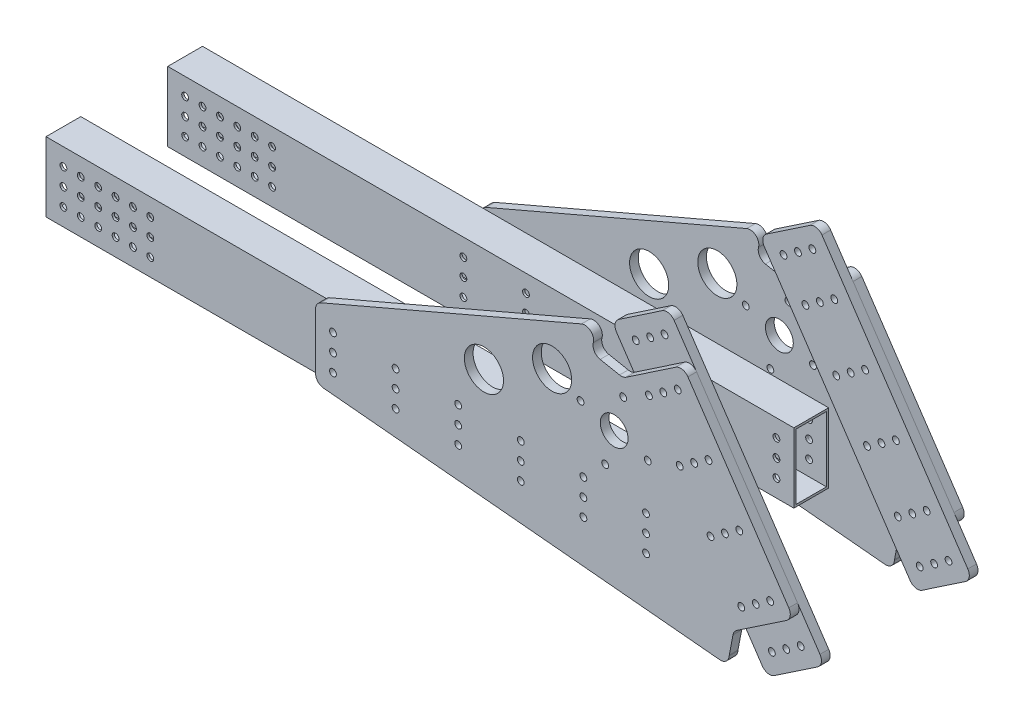
SolidWorks part; units mm, degrees
other "Markup1"
sketch "Sketch2"
sketch "Sketch9" plane through (0, 0, 0) normal (0, 0, 1) x (1, 0, 0)
material "6061-T6 (SS)"
ref_plane "Front Plane" through (0, 0, 0) normal (0, 0, 1) x (1, 0, 0)
ref_plane "Top Plane" through (0, 0, 0) normal (0, 1, 0) x (1, 0, 0)
ref_plane "Right Plane" through (0, 0, 0) normal (1, 0, 0) x (0, 0, -1)
sketch "Grid" plane through (0, 0, 0) normal (0, 0, 1) x (1, 0, 0)
  line L0 (-23.2766, 0) -> (153.3593, 0) construction
  line L1 (0, 0) -> (0, 151.4205) construction
  line L6 (-1009.65, 1168.4) -> (-1009.65, 0) construction
  line L15 (-361.95, 520.7) -> (-803.275, 520.7)
  line L16 (-361.95, 520.7) -> (-361.95, 0)
  line L17 (-361.95, 0) -> (-803.275, 0)
  line L18 (-803.275, 520.7) -> (-803.275, 0)
  line L19 (-803.275, 0) -> (-1244.6, 0)
  line L20 (-803.275, 0) -> (-803.275, 825.5)
  line L21 (-803.275, 825.5) -> (-1244.6, 825.5)
  line L22 (-1244.6, 0) -> (-1244.6, 825.5)
  line L23 (-1030.732, 0) -> (-988.568, 0)
  line L24 (-1030.732, 0) -> (-1030.732, 1168.4)
  line L25 (-1030.732, 1168.4) -> (-988.568, 1168.4)
  line L26 (-988.568, 0) -> (-988.568, 1168.4)
  line L27 (-598.932, 0) -> (-556.768, 0)
  line L28 (-598.932, 0) -> (-598.932, 863.6)
  line L29 (-598.932, 863.6) -> (-556.768, 863.6)
  line L30 (-556.768, 0) -> (-556.768, 863.6)
  line L31 (-577.85, 863.6) -> (-577.85, 0) construction
  line L32 (-361.95, 520.7) -> (-361.95, 596.9) construction
  line L33 (-803.275, 825.5) -> (-803.275, 901.7) construction
  line L34 (-370.0766, 0) -> (-263.7141, 304.8)
  line L35 (-263.7141, 304.8) -> (-157.3516, 0)
  line L36 (-157.3516, 0) -> (-370.0766, 0)
  circle A0 centre (-100.3958, 159.9664) radius 120.65
  dimension "D3" = 241.3
  dimension "D2" = 76.2
  dimension "D4" = 304.8
  dimension "D5" = 212.725
  dimension "D7" = 42.164
  dimension "D8" = 520.7
  dimension "D9" = 304.8
  dimension "D10" = 1168.4
  dimension "D11" = 863.6
  dimension "D12" = 361.95
  dimension "D13" = 577.85
  dimension "D14" = 803.275
  dimension "D15" = 1009.65
sketch "ChassisXY" plane through (0, 0, 0) normal (0, 0, 1) x (1, 0, 0)
  line L0 (755.65, 93.726) -> (95.25, 93.726)
  line L1 (755.65, 93.726) -> (755.65, 42.926)
  line L2 (755.65, 42.926) -> (95.25, 42.926)
  line L3 (95.25, 93.726) -> (95.25, 42.926)
  line L15 (736.7108, 119.126) -> (675.4349, 119.126)
  line L16 (787.4, 42.926) -> (768.35, 42.926)
  line L19 (63.5, 169.926) -> (82.55, 169.926)
  line L20 (736.7108, 119.126) -> (694.5957, 90.719) construction
  line L21 (736.7108, 119.126) -> (717.55, 147.533) construction
  line L22 (694.5957, 90.719) -> (675.4349, 119.126) construction
  line L23 (717.55, 147.533) -> (675.4349, 119.126) construction
  line L27 (63.5, 169.926) -> (63.5, 42.926)
  line L31 (88.9, 42.926) -> (88.9, 1979.9925) construction
  line L32 (62.806, 1979.9925) -> (762, 1979.9925) construction
  line L33 (63.5, 42.926) -> (82.55, 42.926)
  line L36 (88.9, 1320.8) -> (762, 1320.8) construction
  line L37 (88.9, 988.6997) -> (131.0151, 1017.1067) construction
  line L45 (63.5, 42.926) -> (31.75, 42.926)
  line L46 (717.55, 147.533) -> (675.4349, 119.126) construction
  line L47 (717.55, 147.533) -> (-518.4596, 1979.9925) construction
  line L48 (675.4349, 119.126) -> (-560.5747, 1951.5855) construction
  line L49 (-518.4596, 1979.9925) -> (-560.5747, 1951.5855) construction
  line L50 (63.5, 42.926) -> (63.5, 169.926)
  line L51 (0, 74.676) -> (0, 138.176)
  line L52 (31.75, 169.926) -> (63.5, 169.926)
  line L54 (425.45, 93.726) -> (425.45, 42.926) construction
  line L55 (762, 42.926) -> (762, 1979.9925) construction
  line L56 (819.15, 169.926) -> (787.4, 169.926)
  line L57 (850.9, 74.676) -> (850.9, 138.176)
  line L58 (787.4, 42.926) -> (787.4, 169.926)
  line L59 (787.4, 42.926) -> (819.15, 42.926)
  line L60 (82.55, 169.926) -> (82.55, 42.926)
  line L61 (768.35, 169.926) -> (768.35, 42.926)
  line L62 (787.4, 169.926) -> (768.35, 169.926)
  line L63 (787.4, 169.926) -> (787.4, 42.926)
  line L64 (0, 0) -> (0, 200151.4205) construction
  line L65 (-200023.2766, 0) -> (200153.3593, 0) construction
  line L66 (95.25, 152.4) -> (755.65, 152.4) construction
  arc A5 (31.75, 169.926) -> (0, 138.176) centre (31.75, 138.176) ccw
  arc A6 (0, 74.676) -> (31.75, 42.926) centre (31.75, 74.676) ccw
  circle A7 centre (31.75, 74.676) radius 31.75 construction
  circle A8 centre (31.75, 138.176) radius 31.75 construction
  circle A9 centre (819.15, 138.176) radius 31.75 construction
  circle A10 centre (819.15, 74.676) radius 31.75 construction
  arc A11 (850.9, 74.676) -> (819.15, 42.926) centre (819.15, 74.676) cw
  arc A12 (819.15, 169.926) -> (850.9, 138.176) centre (819.15, 138.176) cw
  dimension "D3" = 63.5
  dimension "D1" = 50.8
  dimension "D2" = 56
  dimension "D4" = 38.1
  dimension "D5" = 50.8
  dimension "D6" = 12.7
  dimension "D7" = 19.05
  dimension "D8" = 42.926
  dimension "D9" = 109.474
  dimension "D10" = 25.4
  dimension "D12" = 660.4
  dimension "D13" = 6.35
ref_plane "Plane1" through (561.5696, 378.7835, 0) normal (0.829, 0.5592, 0) x (-0.5592, 0.829, 0)
sketch "carriage geo" plane through (0, 0, 0) normal (0, 0, 1) x (1, 0, 0)
  line L1 (116.0373, 195.326) -> (624.0373, 195.326)
  line L2 (116.0373, 195.326) -> (116.0373, 246.126)
  line L3 (116.0373, 246.126) -> (624.0373, 246.126)
  line L4 (624.0373, 195.326) -> (624.0373, 246.126)
  line L6 (624.0373, 195.326) -> (700.6322, 195.326) construction
  line L17 (717.55, 147.533) -> (-518.4596, 1979.9925) construction
  line L24 (624.0373, 246.126) -> (666.3671, 246.126) construction
  line L33 (666.3671, 246.126) -> (700.6322, 195.326) construction
  line L35 (675.4349, 119.126) -> (-560.5747, 1951.5855) construction
  line L64 (755.65, 93.726) -> (95.25, 93.726) construction
  circle A0 centre (154.1373, 220.726) radius 14.2875
  circle A58 centre (256.8816, 507.741) radius 25.4
  point P4 (353.8882, 537.9448)
  line B0 (120.4355, 364.2548) -> (144.4436, 355.656) construction
  line B1 (345.3934, 565.2279) -> (248.3868, 535.0242)
  line B2 (339.9907, 375.4447) -> (343.9447, 374.0285) construction
  line B3 (348.2442, 386.0326) -> (300.3235, 403.196) construction
  line B4 (308.577, 413.7839) -> (348.5895, 399.4529)
  line B5 (107.1432, 327.1426) -> (206.8255, 291.4401)
  line B6 (112.3162, 360.4178) -> (103.3062, 335.2619)
  line B7 (352.5436, 398.0367) -> (348.5895, 399.4529) construction
  line B8 (366.599, 439.1494) -> (341.413, 442.4393) construction
  line B9 (353.8882, 537.9448) -> (341.413, 442.4393) construction
  line B10 (343.9447, 374.0285) -> (352.5436, 398.0367)
  line B11 (348.5895, 399.4529) -> (308.577, 413.7839)
  line B12 (304.6229, 415.2001) -> (296.0241, 391.1919)
  line B13 (299.9781, 389.7757) -> (339.9907, 375.4447)
  line B14 (140.4752, 344.576) -> (141.8914, 348.5301) construction
  line B15 (129.3385, 325.9381) -> (133.2925, 324.5219) construction
  line B16 (110.7006, 337.0748) -> (109.2844, 333.1207) construction
  line B17 (121.8372, 355.7127) -> (117.8832, 357.1289) construction
  line B18 (117.8832, 357.1289) -> (110.7006, 337.0748)
  line B19 (109.2844, 333.1207) -> (129.3385, 325.9381)
  line B20 (141.8914, 348.5301) -> (121.8372, 355.7127)
  line B21 (133.2925, 324.5219) -> (140.4752, 344.576)
  line B22 (296.0241, 391.1919) -> (299.9781, 389.7757) construction
  line B23 (308.577, 413.7839) -> (304.6229, 415.2001) construction
  arc B24 (248.3868, 535.0242) -> (233.4586, 491.3735) centre (256.8816, 507.741) ccw
  circle B25 centre (256.8816, 507.741) radius 3.1877
  circle B26 centre (353.8882, 537.9448) radius 3.1877
  arc B27 (107.1432, 327.1426) -> (103.3062, 335.2619) centre (109.2844, 333.1207) cw
  circle B28 centre (341.413, 442.4393) radius 30 construction
  arc B29 (121.2422, 363.9009) -> (112.3162, 360.4178) centre (118.2943, 358.2767) ccw
  arc B30 (233.4586, 491.3735) -> (121.2422, 363.9009) centre (161.817, 441.3116) cw
  circle B31 centre (341.413, 442.4393) radius 25.4 construction
  circle B32 centre (366.599, 439.1494) radius 2.4892
  circle B33 centre (338.1231, 417.2533) radius 2.4892
  circle B34 centre (316.2269, 445.7292) radius 2.4892
  circle B35 centre (344.7029, 467.6254) radius 2.4892
  circle B36 centre (341.413, 442.4393) radius 10.16
  circle B37 centre (147.3899, 326.2177) radius 2.4892
  arc B38 (376.4624, 520.4251) -> (367.6342, 457.9958) centre (426.6271, 481.4924) ccw
  arc B39 (367.6342, 457.9958) -> (206.8255, 291.4401) centre (249.6484, 411.0026) cw
  arc B40 (133.2925, 324.5219) -> (129.3385, 325.9381) centre (131.3155, 325.23) cw
  arc B41 (343.9447, 374.0285) -> (339.9907, 375.4447) centre (341.9677, 374.7366) cw
  arc B42 (296.0241, 391.1919) -> (299.9781, 389.7757) centre (298.0011, 390.4838) ccw
  arc B43 (352.5436, 398.0367) -> (348.5895, 399.4529) centre (350.5666, 398.7448) ccw
  arc B44 (304.6229, 415.2001) -> (308.577, 413.7839) centre (306.5999, 414.492) cw
  arc B45 (109.2844, 333.1207) -> (110.7006, 337.0748) centre (109.9925, 335.0977) cw
  arc B46 (117.8832, 357.1289) -> (121.8372, 355.7127) centre (119.8602, 356.4208) cw
  arc B47 (141.8914, 348.5301) -> (140.4752, 344.576) centre (141.1833, 346.553) cw
  circle B48 centre (353.8882, 537.9448) radius 28.575
  line B49 (343.9447, 374.0285) -> (296.1197, 391.1577)
  line B50 (343.9447, 374.0285) -> (318.251, 302.291)
  line B51 (296.1197, 391.1577) -> (270.426, 319.4201)
  line B52 (318.251, 302.291) -> (270.426, 319.4201) construction
  line B53 (141.8571, 348.4344) -> (133.2925, 324.5219) construction
  line B54 (165.7696, 339.8698) -> (237.5071, 314.1761)
  line B55 (157.205, 315.9573) -> (228.9426, 290.2636)
  line B56 (237.5071, 314.1761) -> (228.9426, 290.2636) construction
  line B57 (161.4873, 327.9136) -> (233.2249, 302.2198) construction
  line B58 (165.7696, 339.8698) -> (157.205, 315.9573)
  line B59 (133.2925, 324.5219) -> (157.205, 315.9573) construction
  line B60 (141.8571, 348.4344) -> (165.7696, 339.8698) construction
  line B61 (308.4359, 312.5514) -> (331.9885, 378.3108) construction
  line B62 (320.0322, 382.5931) -> (294.3385, 310.8556) construction
  arc B63 (155.075, 274.6929) -> (165.7608, 168.0174) centre (154.1373, 220.726) ccw
  circle B64 centre (176.5553, 212.6967) radius 2.4892
  circle B65 centre (158.3928, 197.2968) radius 2.4892
  circle B66 centre (135.9748, 205.3261) radius 2.4892
  circle B67 centre (131.7194, 228.7553) radius 2.4892
  circle B68 centre (149.8819, 244.1552) radius 2.4892
  circle B69 centre (172.2999, 236.1259) radius 2.4892
  circle B70 centre (154.1373, 220.726) radius 23.8125 construction
  circle B71 centre (308.4359, 312.5514) radius 2.4892
  arc B72 (165.7608, 168.0174) -> (155.075, 274.6929) centre (154.1373, 220.726) ccw construction
  circle B73 centre (227.2467, 304.361) radius 2.4892
  circle B74 centre (284.5234, 321.116) radius 2.4892
  arc B75 (290.7123, 376.06) -> (193.2811, 330.0162) centre (218.9748, 401.7538) cw
  arc B76 (318.251, 302.291) -> (165.7608, 168.0174) centre (120.5341, 373.1059) cw
  circle B77 centre (312.7182, 324.5077) radius 2.4892
  circle B78 centre (288.8057, 333.0722) radius 2.4892
  circle B79 centre (317.0005, 336.4639) radius 2.4892
  circle B80 centre (293.088, 345.0285) radius 2.4892
  circle B81 centre (321.2828, 348.4202) radius 2.4892
  circle B82 centre (297.3703, 356.9847) radius 2.4892
  circle B83 centre (325.5651, 360.3764) radius 2.4892
  circle B84 centre (301.6526, 368.941) radius 2.4892
  circle B85 centre (329.8473, 372.3327) radius 2.4892
  circle B86 centre (305.9348, 380.8972) radius 2.4892
  arc B87 (162.2796, 314.1398) -> (155.075, 274.6929) centre (155.4279, 295.0098) cw
  circle B88 centre (215.2905, 308.6433) radius 2.4892
  circle B89 centre (203.3342, 312.9256) radius 2.4892
  circle B90 centre (191.378, 317.2079) radius 2.4892
  circle B91 centre (179.4217, 321.4901) radius 2.4892
  circle B92 centre (167.4655, 325.7724) radius 2.4892
  dimension "D2" = 28.575
  dimension "D3" = 25.4
  dimension "D4" = 38.1
  dimension "D8" = 101.6
  dimension "D5" = 50.8
  dimension "D1" = 50.8
  dimension "D6" = 12.7
  dimension "D7" = 508
sketch_block_instance "Block25-1"
sketch_block "Block25"
sketch_block_instance "Block26-1"
sketch_block "Block26"
sketch "carrriageyz" plane through (561.5696, 378.7835, 0) normal (0.829, 0.5592, 0) x (-0.5592, 0.829, 0)
  line L0 (-313.2035, 69.85) -> (769.957, 69.85) construction
  line L1 (769.957, -69.85) -> (-313.2035, -69.85) construction
  line L2 (-262.4035, 69.85) -> (-262.4035, -69.85) construction
  line L4 (-313.2035, 69.85) -> (-313.2035, -69.85) construction
  line L5 (-313.2035, 0) -> (-278.9385, 0) construction
  line L6 (769.957, 69.85) -> (769.957, -69.85) construction
  line L7 (-249.7114, 57.15) -> (-249.7114, 50.8)
  line L8 (-249.7114, 57.15) -> (-97.3114, 57.15)
  line L9 (-249.7114, 50.8) -> (-97.3114, 50.8)
  line L10 (-97.3114, 57.15) -> (-97.3114, 50.8)
  line L11 (1088.9959, 0) -> (-1088.9959, 0) construction
  line L12 (-97.3114, -57.15) -> (-97.3114, -50.8)
  line L13 (-249.7114, -50.8) -> (-97.3114, -50.8)
  line L14 (-249.7114, -57.15) -> (-97.3114, -57.15)
  line L15 (-249.7114, -57.15) -> (-249.7114, -50.8)
  line L16 (-218.5469, 31.75) -> (-148.6639, 31.75)
  line L17 (-174.4547, 57.15) -> (-206.8488, 57.15)
  line L19 (-221.2897, -57.15) -> (-160.0138, -57.15)
  line L21 (-219.5489, -57.15) -> (-127.4739, -57.15)
  line L22 (-219.5489, 63.5) -> (-127.4739, 63.5)
  line L23 (-219.5489, 63.5) -> (-219.5489, 57.15)
  line L24 (-219.5489, 57.15) -> (-127.4739, 57.15)
  line L25 (-127.4739, 63.5) -> (-127.4739, 57.15)
  line L26 (-127.4739, -63.5) -> (-127.4739, -57.15)
  line L27 (-219.5489, -63.5) -> (-127.4739, -63.5)
  line L28 (-219.5489, -63.5) -> (-219.5489, -57.15)
  line L29 (-218.5469, 31.75) -> (-218.5469, -31.75)
  line L30 (-218.5469, -31.75) -> (-148.6639, -31.75)
  line L31 (-148.6639, 31.75) -> (-148.6639, -31.75)
  line L33 (-97.3114, -69.1134) -> (-125.8864, -69.1134)
  line L34 (-97.3114, 57.15) -> (-125.8864, 57.15)
  line L35 (-97.3114, 57.15) -> (-97.3114, 69.1134)
  line L36 (-97.3114, 69.1134) -> (-125.8864, 69.1134)
  line L37 (-125.8864, 57.15) -> (-125.8864, 69.1134)
  line L38 (-249.7114, 57.15) -> (-221.1364, 57.15)
  line L39 (-249.7114, 57.15) -> (-249.7114, 69.1134)
  line L40 (-249.7114, 69.1134) -> (-221.1364, 69.1134)
  line L41 (-221.1364, 57.15) -> (-221.1364, 69.1134)
  line L42 (-125.8864, -57.15) -> (-125.8864, -69.1134)
  line L43 (-97.3114, -57.15) -> (-125.8864, -57.15)
  line L44 (-97.3114, -57.15) -> (-97.3114, -69.1134)
  line L45 (-249.7114, -69.1134) -> (-221.1364, -69.1134)
  line L46 (-221.1364, -57.15) -> (-221.1364, -69.1134)
  line L47 (-249.7114, -57.15) -> (-221.1364, -57.15)
  line L48 (-249.7114, -57.15) -> (-249.7114, -69.1134)
  line L49 (-111.5989, 69.1134) -> (-111.5989, -69.1134) construction
  line L50 (-235.4239, 69.1134) -> (-235.4239, -69.1134) construction
  point P4 (-313.2035, 0)
  point P31 (-148.6639, 0)
  point P41 (-190.6518, 57.15)
  point P53 (-111.5989, 0)
  dimension "D1" = 139.7
  dimension "D2" = 12.7
  dimension "D3" = 6.35
  dimension "D4" = 63.5
  dimension "D5" = 6.35
  dimension "D6" = 152.4
  dimension "D7" = 28.575
  dimension "D8" = 11.9634
  dimension "D9" = 50.8
  dimension "D10" = 1.5875
  dimension "D11" = 1.5875
ref_plane "bearing block interface plane" through (0, 0, 57.15) normal (0, 0, 1) x (1, 0, 0)
sketch "bearing block interface plate" plane through (0, 0, 57.15) normal (0, 0, 1) x (1, 0, 0)
  line L0 (529.0514, 336.1484) -> (571.1665, 364.5554)
  line L1 (529.0514, 336.1484) -> (642.6794, 167.688)
  line L2 (571.1665, 364.5554) -> (684.7945, 196.095)
  line L3 (642.6794, 167.688) -> (684.7945, 196.095)
  line L4 (675.4349, 119.126) -> (-560.5747, 1951.5855) construction
  line L5 (717.55, 147.533) -> (-518.4596, 1979.9925) construction
  line L6 (635.5777, 178.2167) -> (677.6928, 206.6237) construction
  line L7 (585.8654, 251.9182) -> (627.9805, 280.3252) construction
  line L8 (626.7005, 191.3777) -> (668.8156, 219.7847) construction
  line L10 (545.0304, 312.4586) -> (587.1455, 340.8656) construction
  line L12 (528.3092, 320.3288) -> (546.682, 332.7214) construction
  line L15 (606.2073, 289.894) -> (628.6962, 256.5529) construction
  line L16 (522.4272, 322.7212) -> (526.7202, 333.2764) construction
  line L17 (529.0514, 336.1484) -> (536.1532, 325.6196) construction
  line L18 (527.0768, 314.0996) -> (540.247, 311.4938) construction
  line L19 (627.7485, 166.576) -> (639.1433, 166.6024) construction
  line L20 (621.4964, 174.1167) -> (624.014, 187.3041) construction
  circle A0 centre (646.1065, 185.3185) radius 2.4892
  circle A1 centre (656.6352, 192.4202) radius 2.4892
  circle A2 centre (667.164, 199.522) radius 2.4892
  circle A3 centre (567.7395, 346.9249) radius 2.4892
  circle A4 centre (557.2107, 339.8231) radius 2.4892
  circle A5 centre (546.682, 332.7214) radius 2.4892
  arc A7 (522.4272, 322.7212) -> (527.0768, 314.0996) centre (528.3092, 320.3288) ccw construction
  circle A12 centre (562.6609, 309.0316) radius 2.4892
  circle A13 centre (573.1897, 316.1334) radius 2.4892
  circle A14 centre (583.7185, 323.2351) radius 2.4892
  circle A15 centre (606.2073, 289.894) radius 2.4892
  circle A16 centre (595.6786, 282.7922) radius 2.4892
  circle A17 centre (585.1498, 275.6905) radius 2.4892
  circle A18 centre (628.6962, 256.5529) radius 2.4892
  circle A19 centre (618.1674, 249.4511) radius 2.4892
  circle A20 centre (607.6387, 242.3494) radius 2.4892
  circle A21 centre (651.1851, 223.2117) radius 2.4892
  circle A22 centre (640.6563, 216.11) radius 2.4892
  circle A23 centre (630.1275, 209.0082) radius 2.4892
  arc A24 (526.7202, 333.2764) -> (529.0514, 336.1484) centre (532.6023, 330.884) cw construction
  arc A25 (540.247, 311.4938) -> (545.0304, 312.4586) centre (541.4795, 317.723) ccw construction
  arc A26 (639.1433, 166.6024) -> (642.6794, 167.688) centre (639.1286, 172.9523) ccw construction
  arc A27 (627.7485, 166.576) -> (621.4964, 174.1167) centre (627.7337, 172.9259) cw construction
  arc A28 (624.014, 187.3041) -> (626.7005, 191.3777) centre (630.2514, 186.1133) cw construction
  point P28 (617.4518, 273.2234)
  point P64 (0, 0)
  point P70 (671.8417, 223.2117)
  point P71 (668.8156, 219.7847)
  dimension "D3" = 4.9784
  dimension "D8" = 12.7
  dimension "D10" = 2
  dimension "D13" = 6.35
  dimension "D1" = 12.7
  dimension "D2" = 12.7
  dimension "D4" = 12.7
  dimension "D5" = 28.575
  dimension "D6" = 203.2
  dimension "D7" = 4.7625
  dimension "D9" = 9.4615
  dimension "D11" = 4
  dimension "D12" = 12.7
extrude "Boss-Extrude1" add sketch "bearing block interface plate" against normal blind 6.35
fillet "Fillet2" radius 6.35 4 edges at (642.6794, 167.688, 53.975) (571.1665, 364.5554, 53.975) (529.0514, 336.1484, 53.975) (684.7945, 196.095, 53.975)
ref_plane "carriage support plane" through (0, 0, 63.5) normal (0, 0, 1) x (1, 0, 0)
sketch "plate+gb" plane through (0, 0, 63.5) normal (0, 0, 1) x (1, 0, 0)
  line L1 (717.55, 147.533) -> (-518.4596, 1979.9925) construction
  line L3 (116.0373, 195.326) -> (624.0373, 195.326) construction
  line L4 (319.2373, 195.326) -> (627.1295, 166.4772)
  line L7 (668.3717, 220.4428) -> (587.5893, 340.2076)
  line L8 (675.4349, 119.126) -> (-560.5747, 1951.5855) construction
  line L9 (528.9804, 336.2537) -> (319.2373, 246.126)
  line L10 (116.0373, 246.126) -> (624.0373, 246.126) construction
  line L11 (319.2373, 246.126) -> (319.2373, 195.326)
  line L12 (624.0373, 195.326) -> (624.0373, 246.126) construction
  line L13 (587.5893, 340.2076) -> (545.9795, 312.1414)
  line L16 (626.7619, 192.3766) -> (668.3717, 220.4428)
  line L17 (626.7005, 191.3777) -> (668.8156, 219.7847) construction
  line L18 (545.0304, 312.4586) -> (587.1455, 340.8656) construction
  line L20 (441.8031, 281.4461) -> (152.8749, 274.6862) construction
  line L21 (446.7254, 249.5481) -> (169.2, 168.8954) construction
  line L22 (537.2771, 273.9885) -> (543.8511, 298.523) construction
  line L28 (623.8893, 187.3279) -> (621.3716, 174.1405)
  line L29 (627.7488, 166.449) -> (639.1436, 166.4754)
  line L30 (526.6026, 333.3242) -> (522.3095, 322.7691)
  line L31 (527.0521, 313.975) -> (540.2224, 311.3692)
  line L32 (526.6026, 333.3242) -> (522.3095, 322.7691)
  line L33 (527.0521, 313.975) -> (541.1961, 311.1765)
  line L34 (624.0754, 188.303) -> (621.3716, 174.1405)
  circle A0 centre (491.9573, 290.576) radius 14.2875
  circle A1 centre (442.1837, 265.176) radius 14.2875
  arc A2 (155.075, 274.6929) -> (165.7608, 168.0174) centre (154.1373, 220.726) ccw construction
  arc A4 (165.7608, 168.0174) -> (155.075, 274.6929) centre (154.1373, 220.726) ccw construction
  circle A5 centre (537.2771, 273.9885) radius 10.16
  circle A12 centre (537.2771, 273.9885) radius 25.4 construction
  circle A13 centre (537.2771, 273.9885) radius 7.62 construction
  circle A14 centre (491.9573, 290.576) radius 40.64 construction
  circle A15 centre (491.9573, 290.576) radius 15.24 construction
  circle A16 centre (442.1837, 265.176) radius 40.64 construction
  circle A17 centre (442.1837, 265.176) radius 16.2745 construction
  circle A18 centre (543.8511, 298.523) radius 2.4892
  circle A19 centre (561.8116, 267.4145) radius 2.4892
  circle A20 centre (530.7031, 249.4539) radius 2.4892
  circle A21 centre (512.7426, 280.5625) radius 2.4892
  circle A22 centre (651.1851, 223.2117) radius 2.4892 construction
  circle A23 centre (640.6563, 216.11) radius 2.4892 construction
  circle A24 centre (630.1275, 209.0082) radius 2.4892 construction
  circle A25 centre (607.6387, 242.3494) radius 2.4892 construction
  circle A26 centre (618.1674, 249.4511) radius 2.4892 construction
  circle A27 centre (628.6962, 256.5529) radius 2.4892 construction
  circle A28 centre (606.2073, 289.894) radius 2.4892 construction
  circle A29 centre (595.6786, 282.7922) radius 2.4892 construction
  circle A30 centre (585.1498, 275.6905) radius 2.4892 construction
  circle A31 centre (562.6609, 309.0316) radius 2.4892 construction
  circle A32 centre (573.1897, 316.1334) radius 2.4892 construction
  circle A33 centre (583.7185, 323.2351) radius 2.4892 construction
  circle A34 centre (651.1851, 223.2117) radius 2.4892
  circle A37 centre (640.6563, 216.11) radius 2.4892
  circle A40 centre (630.1275, 209.0082) radius 2.4892
  circle A41 centre (607.6387, 242.3494) radius 2.4892
  circle A42 centre (618.1674, 249.4511) radius 2.4892
  circle A43 centre (628.6962, 256.5529) radius 2.4892
  circle A44 centre (606.2073, 289.894) radius 2.4892
  circle A45 centre (595.6786, 282.7922) radius 2.4892
  circle A46 centre (585.1498, 275.6905) radius 2.4892
  circle A47 centre (562.6609, 309.0316) radius 2.4892
  circle A48 centre (573.1897, 316.1334) radius 2.4892
  circle A49 centre (583.7185, 323.2351) radius 2.4892
  arc A57 (541.1961, 311.1765) -> (545.9795, 312.1414) centre (542.4286, 317.4058) ccw
  arc A58 (624.0754, 188.303) -> (626.7619, 192.3766) centre (630.3128, 187.1122) cw
  arc A59 (513.4373, 329.5747) -> (522.0656, 322.0516) centre (515.9443, 323.7406) cw
  arc A60 (626.6295, 191.483) -> (623.8893, 187.3279) centre (630.2514, 186.1133) ccw
  arc A61 (528.9804, 336.2537) -> (526.6026, 333.3242) centre (532.6023, 330.884) ccw
  arc A62 (522.3095, 322.7691) -> (527.0521, 313.975) centre (528.3092, 320.3288) ccw
  arc A63 (540.2224, 311.3692) -> (545.1014, 312.3534) centre (541.4795, 317.723) ccw
  arc A64 (528.9804, 336.2537) -> (526.6026, 333.3242) centre (532.6023, 330.884) ccw
  arc A65 (522.3095, 322.7691) -> (527.0521, 313.975) centre (528.3092, 320.3288) ccw
  arc A66 (621.3716, 174.1405) -> (627.7488, 166.449) centre (627.7337, 172.9259) ccw
  arc A67 (639.1436, 166.4754) -> (642.7505, 167.5827) centre (639.1286, 172.9523) ccw
  arc A68 (626.6295, 191.483) -> (623.8893, 187.3279) centre (630.2514, 186.1133) ccw
  arc A69 (621.3716, 174.1405) -> (627.1295, 166.4772) centre (627.7337, 172.9259) ccw
  point P12 (521.8844, 321.1494)
  point P64 (537.2771, 273.9885)
  dimension "D2" = 50.8
  dimension "D15" = 28.575
  dimension "D16" = 20.32
  dimension "D18" = 4.9784
  dimension "D14" = 6.35
  dimension "D1" = 304.8
  dimension "D9" = 132.08
  dimension "D10" = 27.94
  dimension "D11" = 0.7937
  dimension "D12" = 0.7937
  dimension "D8" = 44.45
  dimension "D19" = 15
  dimension "D20" = 19.05
  dimension "D13" = 0.127
  dimension "D21" = 0.127
  dimension "D17" = 4
extrude "Boss-Extrude2" add sketch "plate+gb" against normal blind 6.35 separate body contours A69 L34 A58 L16 L7 L13 A57 L33 A65 L32 A64 L9 L11 L4 A49 A48 A47 A46 A45 A44 A43 A42 A41 A40 A37 A34 A21 A20 A19 A18 A5 A1 region at (502.2559, 240.3294, 63.5)
fillet "Fillet1" radius 6.35 5 edges at (668.3717, 220.4428, 60.325) (587.5893, 340.2076, 60.325) (319.2373, 246.126, 60.325) (319.2373, 195.326, 60.325) (627.1295, 166.4772, 60.325)
ref_plane "tubeplate" through (0, 0, 57.15) normal (0, 0, 1) x (1, 0, 0)
sketch "tube" plane through (0, 0, 57.15) normal (0, 0, 1) x (1, 0, 0)
  line L0 (116.0373, 246.126) -> (624.0373, 246.126) construction
  line L1 (573.2373, 246.126) -> (116.0373, 246.126)
  line L2 (573.2373, 246.126) -> (573.2373, 195.326)
  line L3 (573.2373, 195.326) -> (116.0373, 195.326)
  line L4 (116.0373, 246.126) -> (116.0373, 195.326)
  line L6 (624.0373, 195.326) -> (624.0373, 246.126) construction
  line L7 (560.5373, 246.126) -> (560.5373, 195.326) construction
  line L8 (319.2373, 246.126) -> (319.2373, 195.326) construction
  line L9 (128.7373, 246.126) -> (128.7373, 195.326) construction
  line L10 (116.0373, 195.326) -> (624.0373, 195.326) construction
  circle A0 centre (560.5373, 220.726) radius 2.4892
  circle A1 centre (560.5373, 208.026) radius 2.4892
  circle A2 centre (560.5373, 233.426) radius 2.4892
  circle A3 centre (514.8173, 208.026) radius 2.4892
  circle A4 centre (514.8173, 220.726) radius 2.4892
  circle A5 centre (514.8173, 233.426) radius 2.4892
  circle A6 centre (469.0973, 208.026) radius 2.4892
  circle A7 centre (469.0973, 220.726) radius 2.4892
  circle A8 centre (469.0973, 233.426) radius 2.4892
  circle A9 centre (423.3773, 208.026) radius 2.4892
  circle A10 centre (423.3773, 220.726) radius 2.4892
  circle A11 centre (423.3773, 233.426) radius 2.4892
  circle A12 centre (377.6573, 208.026) radius 2.4892
  circle A13 centre (377.6573, 220.726) radius 2.4892
  circle A14 centre (377.6573, 233.426) radius 2.4892
  circle A15 centre (331.9373, 208.026) radius 2.4892
  circle A16 centre (331.9373, 220.726) radius 2.4892
  circle A17 centre (331.9373, 233.426) radius 2.4892
  circle A18 centre (128.7373, 220.726) radius 2.4892
  circle A19 centre (128.7373, 208.026) radius 2.4892
  circle A20 centre (128.7373, 233.426) radius 2.4892
  circle A21 centre (141.4373, 220.726) radius 2.4892
  circle A22 centre (141.4373, 208.026) radius 2.4892
  circle A23 centre (141.4373, 233.426) radius 2.4892
  circle A24 centre (154.1373, 220.726) radius 2.4892
  circle A25 centre (154.1373, 208.026) radius 2.4892
  circle A26 centre (154.1373, 233.426) radius 2.4892
  circle A27 centre (166.8373, 220.726) radius 2.4892
  circle A28 centre (166.8373, 208.026) radius 2.4892
  circle A29 centre (166.8373, 233.426) radius 2.4892
  circle A30 centre (179.5373, 220.726) radius 2.4892
  circle A31 centre (179.5373, 208.026) radius 2.4892
  circle A32 centre (179.5373, 233.426) radius 2.4892
  circle A33 centre (192.2373, 220.726) radius 2.4892
  circle A34 centre (192.2373, 208.026) radius 2.4892
  circle A35 centre (192.2373, 233.426) radius 2.4892
  point P89 (0, 0)
  point P90 (0, 0)
  point P91 (0, 0)
  point P92 (0, 0)
  point P93 (0, 0)
  point P94 (0, 0)
  point P95 (0, 0)
  point P96 (0, 0)
  dimension "D3" = 4.9784
  dimension "D8" = 4.9784
  dimension "D1" = 50.8
  dimension "D2" = 12.7
  dimension "D4" = 12.7
  dimension "D5" = 12.7
  dimension "D7" = 12.7
  dimension "D9" = 12.7
  dimension "D10" = 12.7
  dimension "D11" = 12.7
  dimension "D13" = 12.7
  dimension "D6" = 6
  dimension "D12" = 6
extrude "Boss-Extrude3" add sketch "tube" against normal blind 25.4 separate body contours L1 L4 L3 L2 A35 A34 A33 A32 A31 A30 A29 A28 A27 A26 A25 A24 A23 A22 A21 A20 A19 A18 A17 A16 A15 A14 A13 | A2 | A0 | A1 | A3 | A4 | A5 | A8 | A7 | A9 | A6 | A10 | A17 | A14 | A13 | A12 | A15 | A16 | A11 | A35 | A32 | A29 | A26 | A23 | A20 | A18 | A21 | A24 | A27 | A30 | A33 | A34 | A31 | A28 | A25 | A22 | A19 region at (345.9214, 220.726, 57.15) region at (560.5373, 220.726, 57.15) region at (560.5373, 208.026, 57.15) region at (560.5373, 233.426, 57.15) region at (514.8173, 208.026, 57.15) region at (514.8173, 220.726, 57.15) region at (514.8173, 233.426, 57.15) region at (469.0973, 208.026, 57.15) region at (469.0973, 220.726, 57.15) region at (469.0973, 233.426, 57.15) region at (423.3773, 208.026, 57.15) region at (423.3773, 220.726, 57.15) region at (423.3773, 233.426, 57.15) region at (377.6573, 208.026, 57.15) region at (377.6573, 220.726, 57.15) region at (377.6573, 233.426, 57.15) region at (331.9373, 208.026, 57.15) region at (331.9373, 220.726, 57.15) region at (331.9373, 233.426, 57.15) region at (128.7373, 220.726, 57.15) region at (128.7373, 208.026, 57.15) region at (128.7373, 233.426, 57.15) region at (141.4373, 220.726, 57.15) region at (141.4373, 208.026, 57.15) region at (141.4373, 233.426, 57.15) region at (154.1373, 220.726, 57.15) region at (154.1373, 208.026, 57.15) region at (154.1373, 233.426, 57.15) region at (166.8373, 220.726, 57.15) region at (166.8373, 208.026, 57.15) region at (166.8373, 233.426, 57.15) region at (179.5373, 220.726, 57.15) region at (179.5373, 208.026, 57.15) region at (179.5373, 233.426, 57.15) region at (192.2373, 220.726, 57.15) region at (192.2373, 208.026, 57.15) region at (192.2373, 233.426, 57.15)
shell "Shell2" thickness 1.5875 removed face at (573.2373, 220.726, 44.45) removed face at (116.0373, 220.726, 44.45)
extrude "Cut-Extrude2" cut sketch "tube<4>" against normal through all contours A2 | A0 | A1 | A3 | A4 | A5 | A8 | A7 | A10 | A11 | A14 | A12 | A17 | A16 | A35 | A34 | A32 | A30 | A29 | A27 | A24 | A22 | A19 | A31 | A6 | A9 | A13 | A15 | A33 | A26 | A23 | A20 | A18 | A21 | A25 | A28 region at (560.5373, 220.726, 57.15) region at (560.5373, 208.026, 57.15) region at (560.5373, 233.426, 57.15) region at (514.8173, 208.026, 57.15) region at (514.8173, 220.726, 57.15) region at (514.8173, 233.426, 57.15) region at (469.0973, 220.726, 57.15) region at (469.0973, 233.426, 57.15) region at (423.3773, 220.726, 57.15) region at (423.3773, 233.426, 57.15) region at (377.6573, 208.026, 57.15) region at (377.6573, 233.426, 57.15) region at (331.9373, 220.726, 57.15) region at (331.9373, 233.426, 57.15) region at (128.7373, 208.026, 57.15) region at (141.4373, 208.026, 57.15) region at (154.1373, 220.726, 57.15) region at (166.8373, 220.726, 57.15) region at (166.8373, 233.426, 57.15) region at (179.5373, 220.726, 57.15) region at (179.5373, 208.026, 57.15) region at (179.5373, 233.426, 57.15) region at (192.2373, 208.026, 57.15) region at (192.2373, 233.426, 57.15)
sketch "tube<4>" plane through (0, 0, 57.15) normal (0, 0, 1) x (1, 0, 0) same geometry as "tube"
sketch "Sketch10" plane through (0, 0, 63.5) normal (0, 0, 1) x (1, 0, 0)
  circle A0 centre (469.0973, 208.026) radius 2.4892 construction
  circle A1 centre (423.3773, 208.026) radius 2.4892 construction
  circle A2 centre (377.6573, 208.026) radius 2.4892 construction
  circle A3 centre (331.9373, 208.026) radius 2.4892 construction
  circle A4 centre (331.9373, 220.726) radius 2.4892 construction
  circle A5 centre (377.6573, 220.726) radius 2.4892 construction
  circle A6 centre (423.3773, 220.726) radius 2.4892 construction
  circle A7 centre (469.0973, 220.726) radius 2.4892 construction
  circle A8 centre (514.8173, 220.726) radius 2.4892 construction
  circle A9 centre (514.8173, 208.026) radius 2.4892 construction
  circle A10 centre (560.5373, 208.026) radius 2.4892 construction
  circle A11 centre (560.5373, 220.726) radius 2.4892 construction
  circle A12 centre (560.5373, 233.426) radius 2.4892 construction
  circle A13 centre (514.8173, 233.426) radius 2.4892 construction
  circle A14 centre (469.0973, 233.426) radius 2.4892 construction
  circle A15 centre (423.3773, 233.426) radius 2.4892 construction
  circle A16 centre (377.6573, 233.426) radius 2.4892 construction
  circle A17 centre (331.9373, 233.426) radius 2.4892 construction
  circle A18 centre (469.0973, 208.026) radius 2.4892
  circle A19 centre (423.3773, 208.026) radius 2.4892
  circle A20 centre (377.6573, 208.026) radius 2.4892
  circle A21 centre (331.9373, 208.026) radius 2.4892
  circle A22 centre (331.9373, 220.726) radius 2.4892
  circle A23 centre (377.6573, 220.726) radius 2.4892
  circle A24 centre (423.3773, 220.726) radius 2.4892
  circle A25 centre (469.0973, 220.726) radius 2.4892
  circle A26 centre (514.8173, 220.726) radius 2.4892
  circle A27 centre (514.8173, 208.026) radius 2.4892
  circle A28 centre (560.5373, 208.026) radius 2.4892
  circle A29 centre (560.5373, 220.726) radius 2.4892
  circle A30 centre (560.5373, 233.426) radius 2.4892
  circle A31 centre (514.8173, 233.426) radius 2.4892
  circle A32 centre (469.0973, 233.426) radius 2.4892
  circle A33 centre (423.3773, 233.426) radius 2.4892
  circle A34 centre (377.6573, 233.426) radius 2.4892
  circle A35 centre (331.9373, 233.426) radius 2.4892
extrude "Cut-Extrude3" cut sketch "Sketch10" against normal through all
mirror "Mirror1" about plane through (0, 0, 0) normal (0, 0, 1) of bodies 105 104 101
equation "\"D3@plate+gb\" = 12 / 20"
equation "\"D4@plate+gb\" = 64 / 20"
equation "\"D5@plate+gb\" = 24 / 20"
equation "\"D6@plate+gb\" = 64 / 20"
equation "\"D7@plate+gb\" = 0.25 /  ( sin ( 180 / 16 )  ) "
